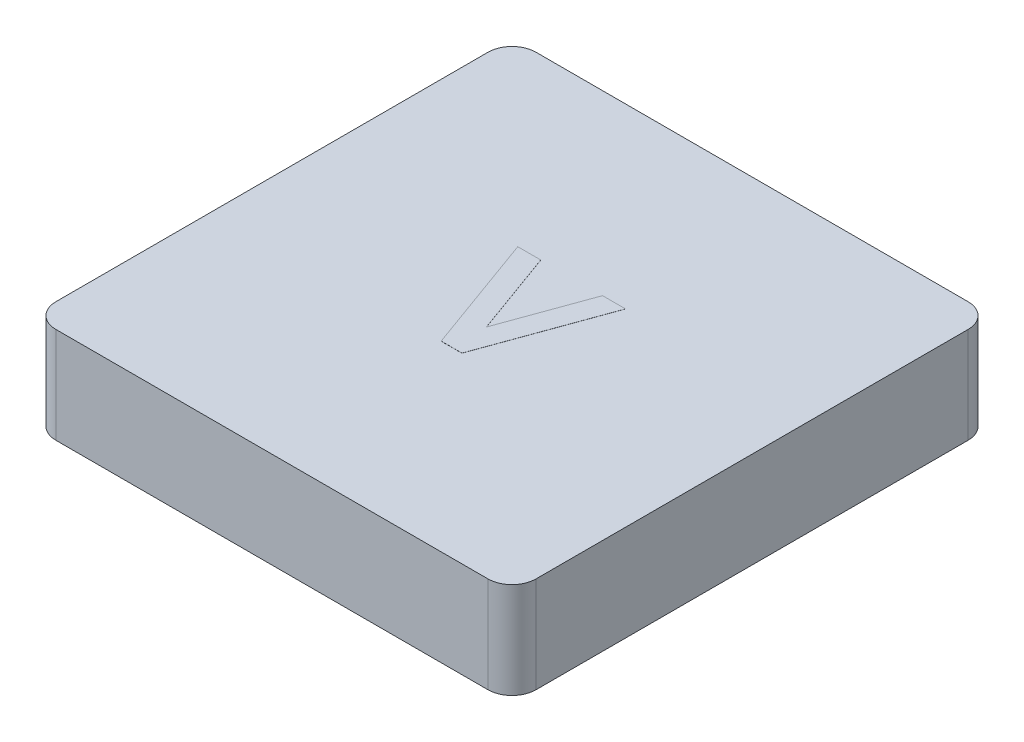
SolidWorks part; units mm, degrees
ref_plane "Front Plane" through (0, 0, 0) normal (0, 0, 1) x (1, 0, 0)
ref_plane "Top Plane" through (0, 0, 0) normal (0, 1, 0) x (1, 0, 0)
ref_plane "Right Plane" through (0, 0, 0) normal (1, 0, 0) x (0, 0, -1)
sketch "Sketch1" plane through (0, 0, 0) normal (0, 1, 0) x (1, 0, 0)
  line L0 (0, 0) -> (12.7, 0)
  line L1 (12.7, 0) -> (12.7, 12.7)
  line L2 (12.7, 12.7) -> (0, 12.7)
  line L3 (0, 12.7) -> (0, 0)
  dimension "D1" = 12.7
  dimension "D2" = 12.7
extrude "Boss-Extrude1" add sketch "Sketch1" along normal blind 2.54
fillet "Fillet1" radius 0.635 4 edges at (0, 1.27, -12.7) (12.7, 1.27, -12.7) (12.7, 1.27, 0) (0, 1.27, 0)
shell "Shell1" thickness 0.635 removed face at (6.35, 0, -6.35)
sketch "Sketch2" plane through (0, 1.905, 0) normal (0, -1, 0) x (-1, 0, 0)
  line L0 (-0.635, 6.35) -> (-12.065, 6.35) construction
  line L1 (-0.635, 12.065) -> (-0.635, 0.635) construction
  line L2 (-12.065, 0.635) -> (-12.065, 12.065) construction
  line L3 (-6.35, 0.635) -> (-6.35, 12.065) construction
  line L4 (-0.635, 0.635) -> (-12.065, 0.635) construction
  line L5 (-12.065, 12.065) -> (-0.635, 12.065) construction
  circle A0 centre (-6.35, 6.35) radius 2.54
  dimension "D1" = 5.08
extrude "Boss-Extrude2" add sketch "Sketch2" along normal up to surface (1.905 mm away) up to face at (6.35, 0, -6.35)
sketch "Sketch3" plane through (0, 2.54, 0) normal (0, 1, 0) x (1, 0, 0)
  line L0 (0, 12.065) -> (0, 0.635) construction
  line L1 (0.635, 0) -> (12.065, 0) construction
  text T0 "<b>V</b>"
  point P1 (0, 0)
  dimension "D1" = 4.7498
  dimension "D2" = 4.826
extrude "Boss-Extrude3" add sketch "Sketch3" along normal blind 0.0025
